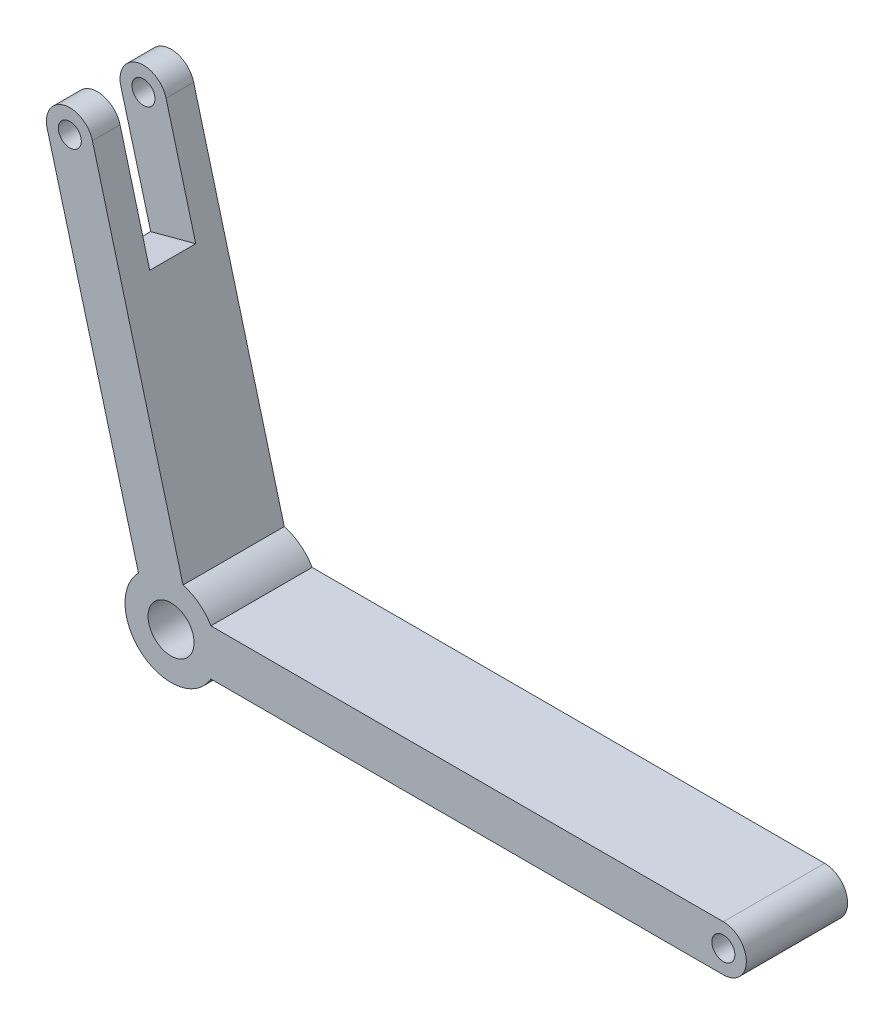
SolidWorks part; units mm, degrees
ref_plane "前视基准面" through (0, 0, 0) normal (0, 0, 1) x (1, 0, 0)
ref_plane "上视基准面" through (0, 0, 0) normal (0, 1, 0) x (1, 0, 0)
ref_plane "右视基准面" through (0, 0, 0) normal (1, 0, 0) x (0, 0, -1)
sketch "草图1" plane through (0, 0, 0) normal (0, 0, 1) x (1, 0, 0)
  line L0 (78.0004, 117.1037) -> (100, 35) construction
  line L1 (100, 35) -> (220, 35) construction
  line L2 (82.9161, 118.4154) -> (102.5982, 44.6566)
  line L3 (108.6603, 40) -> (220, 40)
  line L4 (92.9216, 42.0638) -> (73.0874, 115.7818)
  line L5 (108.6603, 30) -> (220, 30)
  arc A0 (82.9161, 118.4154) -> (73.0874, 115.7818) centre (78.0004, 117.1037) ccw
  arc A2 (220, 30) -> (220, 40) centre (220, 35) ccw
  circle A3 centre (78.0004, 117.1037) radius 2.5
  circle A5 centre (220, 35) radius 2.5
  arc A6 (92.9216, 42.0638) -> (108.6603, 30) centre (100, 35) ccw
  arc A8 (108.6603, 40) -> (102.5982, 44.6566) centre (100, 35) ccw
  circle A9 centre (100, 35) radius 5
  dimension "D1" = 105
  dimension "D2" = 85
  dimension "D3" = 120
extrude "凸台-拉伸1" add sketch "草图1" along normal mid plane 22
extrude "凸台-拉伸2" add sketch "草图1<2>" along normal mid plane 22 contours L3 A8 L2 A0 L4 A6 L5 A2 A3 A5 region at (91.0133, 81.0707, 0)
sketch "草图1<2>" plane through (0, 0, 0) normal (0, 0, 1) x (1, 0, 0) same geometry as "草图1"
sketch "草图3" plane through (0, 0, 0) normal (0, 0, 1) x (1, 0, 0)
  line L0 (102.5982, 44.6566) -> (82.9161, 118.4154) construction
  line L1 (73.0874, 115.7818) -> (92.9216, 42.0638) construction
  line L2 (89.3617, 94.2606) -> (82.9161, 118.4154)
  line L3 (73.0874, 115.7818) -> (79.58, 91.6505)
  line L4 (79.58, 91.6505) -> (89.3617, 94.2606)
  circle A1 centre (78.0004, 117.1037) radius 2.5
  arc A2 (82.9161, 118.4154) -> (73.0874, 115.7818) centre (78.0004, 117.1037) ccw
  dimension "D1" = 25
extrude "切除-拉伸1" cut sketch "草图3" against normal mid plane 10
